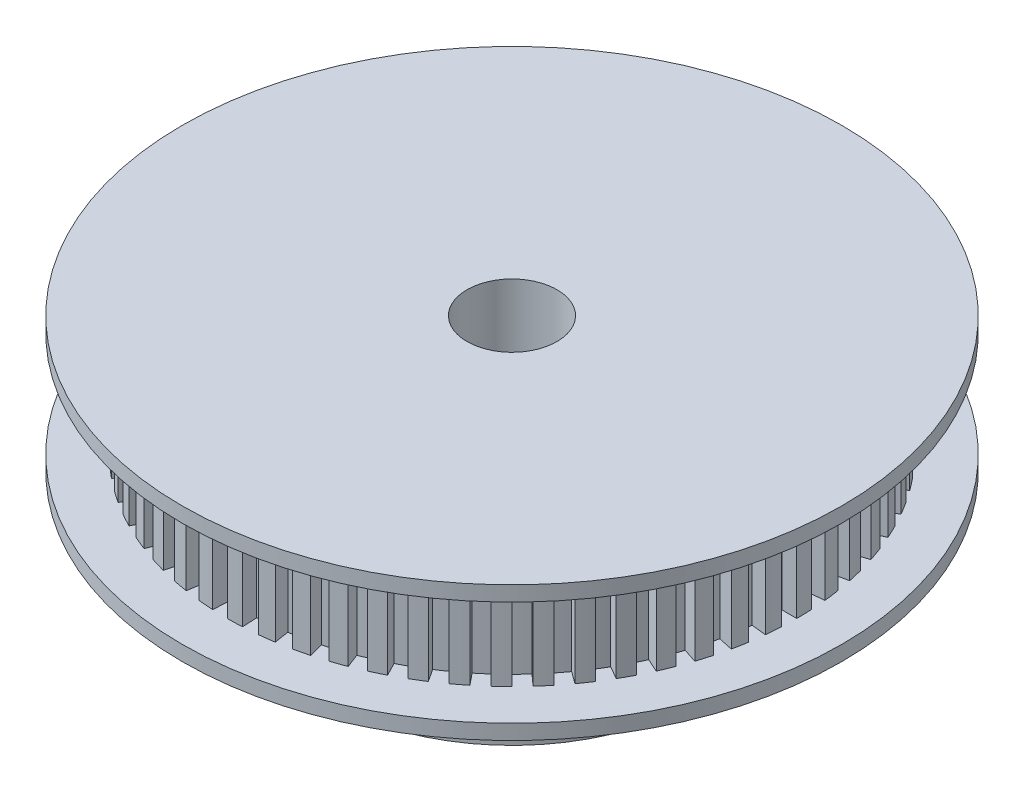
SolidWorks part; units mm, degrees
ref_plane "Front Plane" through (0, 0, 0) normal (0, 0, 1) x (1, 0, 0)
ref_plane "Top Plane" through (0, 0, 0) normal (0, 1, 0) x (1, 0, 0)
ref_plane "Right Plane" through (0, 0, 0) normal (1, 0, 0) x (0, 0, -1)
sketch "Sketch1" plane through (0, 0, 0) normal (0, 1, 0) x (1, 0, 0)
  line L1 (-12.5, -12.5) -> (12.5, -12.5)
  line L2 (-12.5, -12.5) -> (-12.5, 12.5)
  line L3 (-12.5, 12.5) -> (12.5, 12.5)
  line L4 (12.5, -12.5) -> (12.5, 12.5)
  line L5 (-12.5, -12.5) -> (12.5, 12.5) construction
  line L6 (-12.5, 12.5) -> (12.5, -12.5) construction
extrude "Boss-Extrude1" add sketch "Sketch1" along normal blind 7
sketch "Sketch2" plane through (0, 7, 0) normal (0, 1, 0) x (1, 0, 0)
  circle A0 centre (0, 0) radius 22
  dimension "D1" = 44
extrude "Boss-Extrude2" add sketch "Sketch2" along normal blind 1
sketch "Sketch4" plane through (0, 8, 0) normal (0, 1, 0) x (1, 0, 0)
  line L0 (0, 19) -> (0, 18)
  line L1 (0.9944, 18.974) -> (0.942, 17.9753)
  line L2 (1.986, 18.8959) -> (1.8815, 17.9014)
  line L3 (2.9723, 18.7661) -> (2.8158, 17.7784)
  line L4 (3.9503, 18.5848) -> (3.7424, 17.6067)
  line L5 (4.9176, 18.3526) -> (4.6587, 17.3867)
  line L6 (5.8713, 18.0701) -> (5.5623, 17.119)
  line L7 (6.809, 17.738) -> (6.4506, 16.8044)
  line L8 (7.728, 17.3574) -> (7.3213, 16.4438)
  line L9 (8.6258, 16.9291) -> (8.1718, 16.0381)
  line L10 (9.5, 16.4545) -> (9, 15.5885)
  line L11 (10.3481, 15.9347) -> (9.8035, 15.0961)
  line L12 (11.1679, 15.3713) -> (10.5801, 14.5623)
  line L13 (11.9571, 14.7658) -> (11.3278, 13.9886)
  line L14 (12.7135, 14.1198) -> (12.0444, 13.3766)
  line L15 (13.435, 13.435) -> (12.7279, 12.7279)
  line L16 (14.1198, 12.7135) -> (13.3766, 12.0444)
  line L17 (14.7658, 11.9571) -> (13.9886, 11.3278)
  line L18 (15.3713, 11.1679) -> (14.5623, 10.5801)
  line L19 (15.9347, 10.3481) -> (15.0961, 9.8035)
  line L20 (16.4545, 9.5) -> (15.5885, 9)
  line L21 (16.9291, 8.6258) -> (16.0381, 8.1718)
  line L22 (17.3574, 7.728) -> (16.4438, 7.3213)
  line L23 (17.738, 6.809) -> (16.8044, 6.4506)
  line L24 (18.0701, 5.8713) -> (17.119, 5.5623)
  line L25 (18.3526, 4.9176) -> (17.3867, 4.6587)
  line L26 (18.5848, 3.9503) -> (17.6067, 3.7424)
  line L27 (18.7661, 2.9723) -> (17.7784, 2.8158)
  line L28 (18.8959, 1.986) -> (17.9014, 1.8815)
  line L29 (18.974, 0.9944) -> (17.9753, 0.942)
  line L30 (19, 0) -> (18, 0)
  line L31 (18.974, -0.9944) -> (17.9753, -0.942)
  line L32 (18.8959, -1.986) -> (17.9014, -1.8815)
  line L33 (18.7661, -2.9723) -> (17.7784, -2.8158)
  line L34 (18.5848, -3.9503) -> (17.6067, -3.7424)
  line L35 (18.3526, -4.9176) -> (17.3867, -4.6587)
  line L36 (18.0701, -5.8713) -> (17.119, -5.5623)
  line L37 (17.738, -6.809) -> (16.8044, -6.4506)
  line L38 (17.3574, -7.728) -> (16.4438, -7.3213)
  line L39 (16.9291, -8.6258) -> (16.0381, -8.1718)
  line L40 (16.4545, -9.5) -> (15.5885, -9)
  line L41 (15.9347, -10.3481) -> (15.0961, -9.8035)
  line L42 (15.3713, -11.1679) -> (14.5623, -10.5801)
  line L43 (14.7658, -11.9571) -> (13.9886, -11.3278)
  line L44 (14.1198, -12.7135) -> (13.3766, -12.0444)
  line L45 (13.435, -13.435) -> (12.7279, -12.7279)
  line L46 (12.7135, -14.1198) -> (12.0444, -13.3766)
  line L47 (11.9571, -14.7658) -> (11.3278, -13.9886)
  line L48 (11.1679, -15.3713) -> (10.5801, -14.5623)
  line L49 (10.3481, -15.9347) -> (9.8035, -15.0961)
  line L50 (9.5, -16.4545) -> (9, -15.5885)
  line L51 (8.6258, -16.9291) -> (8.1718, -16.0381)
  line L52 (7.728, -17.3574) -> (7.3213, -16.4438)
  line L53 (6.809, -17.738) -> (6.4506, -16.8044)
  line L54 (5.8713, -18.0701) -> (5.5623, -17.119)
  line L55 (4.9176, -18.3526) -> (4.6587, -17.3867)
  line L56 (3.9503, -18.5848) -> (3.7424, -17.6067)
  line L57 (2.9723, -18.7661) -> (2.8158, -17.7784)
  line L58 (1.986, -18.8959) -> (1.8815, -17.9014)
  line L59 (0.9944, -18.974) -> (0.942, -17.9753)
  line L60 (0, -19) -> (0, -18)
  line L61 (-0.9944, -18.974) -> (-0.942, -17.9753)
  line L62 (-1.986, -18.8959) -> (-1.8815, -17.9014)
  line L63 (-2.9723, -18.7661) -> (-2.8158, -17.7784)
  line L64 (-3.9503, -18.5848) -> (-3.7424, -17.6067)
  line L65 (-4.9176, -18.3526) -> (-4.6587, -17.3867)
  line L66 (-5.8713, -18.0701) -> (-5.5623, -17.119)
  line L67 (-6.809, -17.738) -> (-6.4506, -16.8044)
  line L68 (-7.728, -17.3574) -> (-7.3213, -16.4438)
  line L69 (-8.6258, -16.9291) -> (-8.1718, -16.0381)
  line L70 (-9.5, -16.4545) -> (-9, -15.5885)
  line L71 (-10.3481, -15.9347) -> (-9.8035, -15.0961)
  line L72 (-11.1679, -15.3713) -> (-10.5801, -14.5623)
  line L73 (-11.9571, -14.7658) -> (-11.3278, -13.9886)
  line L74 (-12.7135, -14.1198) -> (-12.0444, -13.3766)
  line L75 (-13.435, -13.435) -> (-12.7279, -12.7279)
  line L76 (-14.1198, -12.7135) -> (-13.3766, -12.0444)
  line L77 (-14.7658, -11.9571) -> (-13.9886, -11.3278)
  line L78 (-15.3713, -11.1679) -> (-14.5623, -10.5801)
  line L79 (-15.9347, -10.3481) -> (-15.0961, -9.8035)
  line L80 (-16.4545, -9.5) -> (-15.5885, -9)
  line L81 (-16.9291, -8.6258) -> (-16.0381, -8.1718)
  line L82 (-17.3574, -7.728) -> (-16.4438, -7.3213)
  line L83 (-17.738, -6.809) -> (-16.8044, -6.4506)
  line L84 (-18.0701, -5.8713) -> (-17.119, -5.5623)
  line L85 (-18.3526, -4.9176) -> (-17.3867, -4.6587)
  line L86 (-18.5848, -3.9503) -> (-17.6067, -3.7424)
  line L87 (-18.7661, -2.9723) -> (-17.7784, -2.8158)
  line L88 (-18.8959, -1.986) -> (-17.9014, -1.8815)
  line L89 (-18.974, -0.9944) -> (-17.9753, -0.942)
  line L90 (-19, 0) -> (-18, 0)
  line L91 (-18.974, 0.9944) -> (-17.9753, 0.942)
  line L92 (-18.8959, 1.986) -> (-17.9014, 1.8815)
  line L93 (-18.7661, 2.9723) -> (-17.7784, 2.8158)
  line L94 (-18.5848, 3.9503) -> (-17.6067, 3.7424)
  line L95 (-18.3526, 4.9176) -> (-17.3867, 4.6587)
  line L96 (-18.0701, 5.8713) -> (-17.119, 5.5623)
  line L97 (-17.738, 6.809) -> (-16.8044, 6.4506)
  line L98 (-17.3574, 7.728) -> (-16.4438, 7.3213)
  line L99 (-16.9291, 8.6258) -> (-16.0381, 8.1718)
  line L100 (-16.4545, 9.5) -> (-15.5885, 9)
  line L101 (-15.9347, 10.3481) -> (-15.0961, 9.8035)
  line L102 (-15.3713, 11.1679) -> (-14.5623, 10.5801)
  line L103 (-14.7658, 11.9571) -> (-13.9886, 11.3278)
  line L104 (-14.1198, 12.7135) -> (-13.3766, 12.0444)
  line L105 (-13.435, 13.435) -> (-12.7279, 12.7279)
  line L106 (-12.7135, 14.1198) -> (-12.0444, 13.3766)
  line L107 (-11.9571, 14.7658) -> (-11.3278, 13.9886)
  line L108 (-11.1679, 15.3713) -> (-10.5801, 14.5623)
  line L109 (-10.3481, 15.9347) -> (-9.8035, 15.0961)
  line L110 (-9.5, 16.4545) -> (-9, 15.5885)
  line L111 (-8.6258, 16.9291) -> (-8.1718, 16.0381)
  line L112 (-7.728, 17.3574) -> (-7.3213, 16.4438)
  line L113 (-6.809, 17.738) -> (-6.4506, 16.8044)
  line L114 (-5.8713, 18.0701) -> (-5.5623, 17.119)
  line L115 (-4.9176, 18.3526) -> (-4.6587, 17.3867)
  line L116 (-3.9503, 18.5848) -> (-3.7424, 17.6067)
  line L117 (-2.9723, 18.7661) -> (-2.8158, 17.7784)
  line L118 (-1.986, 18.8959) -> (-1.8815, 17.9014)
  line L119 (-0.9944, 18.974) -> (-0.942, 17.9753)
  arc A2 (0.9944, 18.974) -> (1.986, 18.8959) centre (0, 0) cw
  arc A3 (1.8815, 17.9014) -> (2.8158, 17.7784) centre (0, 0) cw
  arc A4 (3.7424, 17.6067) -> (4.6587, 17.3867) centre (0, 0) cw
  arc A5 (2.9723, 18.7661) -> (3.9503, 18.5848) centre (0, 0) cw
  arc A6 (5.5623, 17.119) -> (6.4506, 16.8044) centre (0, 0) cw
  arc A7 (4.9176, 18.3526) -> (5.8713, 18.0701) centre (0, 0) cw
  arc A8 (7.3213, 16.4438) -> (8.1718, 16.0381) centre (0, 0) cw
  arc A9 (6.809, 17.738) -> (7.728, 17.3574) centre (0, 0) cw
  arc A10 (9, 15.5885) -> (9.8035, 15.0961) centre (0, 0) cw
  arc A11 (8.6258, 16.9291) -> (9.5, 16.4545) centre (0, 0) cw
  arc A12 (10.5801, 14.5623) -> (11.3278, 13.9886) centre (0, 0) cw
  arc A13 (10.3481, 15.9347) -> (11.1679, 15.3713) centre (0, 0) cw
  arc A14 (12.0444, 13.3766) -> (12.7279, 12.7279) centre (0, 0) cw
  arc A15 (11.9571, 14.7658) -> (12.7135, 14.1198) centre (0, 0) cw
  arc A16 (13.3766, 12.0444) -> (13.9886, 11.3278) centre (0, 0) cw
  arc A17 (13.435, 13.435) -> (14.1198, 12.7135) centre (0, 0) cw
  arc A18 (14.5623, 10.5801) -> (15.0961, 9.8035) centre (0, 0) cw
  arc A19 (14.7658, 11.9571) -> (15.3713, 11.1679) centre (0, 0) cw
  arc A20 (15.5885, 9) -> (16.0381, 8.1718) centre (0, 0) cw
  arc A21 (15.9347, 10.3481) -> (16.4545, 9.5) centre (0, 0) cw
  arc A22 (16.4438, 7.3213) -> (16.8044, 6.4506) centre (0, 0) cw
  arc A23 (16.9291, 8.6258) -> (17.3574, 7.728) centre (0, 0) cw
  arc A24 (17.119, 5.5623) -> (17.3867, 4.6587) centre (0, 0) cw
  arc A25 (17.738, 6.809) -> (18.0701, 5.8713) centre (0, 0) cw
  arc A26 (17.6067, 3.7424) -> (17.7784, 2.8158) centre (0, 0) cw
  arc A27 (18.3526, 4.9176) -> (18.5848, 3.9503) centre (0, 0) cw
  arc A28 (17.9014, 1.8815) -> (17.9753, 0.942) centre (0, 0) cw
  arc A29 (18.7661, 2.9723) -> (18.8959, 1.986) centre (0, 0) cw
  arc A30 (18, 0) -> (17.9753, -0.942) centre (0, 0) cw
  arc A31 (18.974, 0.9944) -> (19, 0) centre (0, 0) cw
  arc A32 (17.9014, -1.8815) -> (17.7784, -2.8158) centre (0, 0) cw
  arc A33 (18.974, -0.9944) -> (18.8959, -1.986) centre (0, 0) cw
  arc A34 (17.6067, -3.7424) -> (17.3867, -4.6587) centre (0, 0) cw
  arc A35 (18.7661, -2.9723) -> (18.5848, -3.9503) centre (0, 0) cw
  arc A36 (17.119, -5.5623) -> (16.8044, -6.4506) centre (0, 0) cw
  arc A37 (18.3526, -4.9176) -> (18.0701, -5.8713) centre (0, 0) cw
  arc A38 (16.4438, -7.3213) -> (16.0381, -8.1718) centre (0, 0) cw
  arc A39 (17.738, -6.809) -> (17.3574, -7.728) centre (0, 0) cw
  arc A40 (15.5885, -9) -> (15.0961, -9.8035) centre (0, 0) cw
  arc A41 (16.9291, -8.6258) -> (16.4545, -9.5) centre (0, 0) cw
  arc A42 (14.5623, -10.5801) -> (13.9886, -11.3278) centre (0, 0) cw
  arc A43 (15.9347, -10.3481) -> (15.3713, -11.1679) centre (0, 0) cw
  arc A44 (13.3766, -12.0444) -> (12.7279, -12.7279) centre (0, 0) cw
  arc A45 (14.7658, -11.9571) -> (14.1198, -12.7135) centre (0, 0) cw
  arc A46 (12.0444, -13.3766) -> (11.3278, -13.9886) centre (0, 0) cw
  arc A47 (13.435, -13.435) -> (12.7135, -14.1198) centre (0, 0) cw
  arc A48 (10.5801, -14.5623) -> (9.8035, -15.0961) centre (0, 0) cw
  arc A49 (11.9571, -14.7658) -> (11.1679, -15.3713) centre (0, 0) cw
  arc A50 (9, -15.5885) -> (8.1718, -16.0381) centre (0, 0) cw
  arc A51 (10.3481, -15.9347) -> (9.5, -16.4545) centre (0, 0) cw
  arc A52 (7.3213, -16.4438) -> (6.4506, -16.8044) centre (0, 0) cw
  arc A53 (8.6258, -16.9291) -> (7.728, -17.3574) centre (0, 0) cw
  arc A54 (5.5623, -17.119) -> (4.6587, -17.3867) centre (0, 0) cw
  arc A55 (6.809, -17.738) -> (5.8713, -18.0701) centre (0, 0) cw
  arc A56 (3.7424, -17.6067) -> (2.8158, -17.7784) centre (0, 0) cw
  arc A57 (4.9176, -18.3526) -> (3.9503, -18.5848) centre (0, 0) cw
  arc A58 (1.8815, -17.9014) -> (0.942, -17.9753) centre (0, 0) cw
  arc A59 (2.9723, -18.7661) -> (1.986, -18.8959) centre (0, 0) cw
  arc A60 (0, -18) -> (-0.942, -17.9753) centre (0, 0) cw
  arc A61 (0.9944, -18.974) -> (0, -19) centre (0, 0) cw
  arc A62 (-1.8815, -17.9014) -> (-2.8158, -17.7784) centre (0, 0) cw
  arc A63 (-0.9944, -18.974) -> (-1.986, -18.8959) centre (0, 0) cw
  arc A64 (-3.7424, -17.6067) -> (-4.6587, -17.3867) centre (0, 0) cw
  arc A65 (-2.9723, -18.7661) -> (-3.9503, -18.5848) centre (0, 0) cw
  arc A66 (-5.5623, -17.119) -> (-6.4506, -16.8044) centre (0, 0) cw
  arc A67 (-4.9176, -18.3526) -> (-5.8713, -18.0701) centre (0, 0) cw
  arc A68 (-7.3213, -16.4438) -> (-8.1718, -16.0381) centre (0, 0) cw
  arc A69 (-6.809, -17.738) -> (-7.728, -17.3574) centre (0, 0) cw
  arc A70 (-9, -15.5885) -> (-9.8035, -15.0961) centre (0, 0) cw
  arc A71 (-8.6258, -16.9291) -> (-9.5, -16.4545) centre (0, 0) cw
  arc A72 (-10.5801, -14.5623) -> (-11.3278, -13.9886) centre (0, 0) cw
  arc A73 (-10.3481, -15.9347) -> (-11.1679, -15.3713) centre (0, 0) cw
  arc A74 (-12.0444, -13.3766) -> (-12.7279, -12.7279) centre (0, 0) cw
  arc A75 (-11.9571, -14.7658) -> (-12.7135, -14.1198) centre (0, 0) cw
  arc A76 (-13.3766, -12.0444) -> (-13.9886, -11.3278) centre (0, 0) cw
  arc A77 (-13.435, -13.435) -> (-14.1198, -12.7135) centre (0, 0) cw
  arc A78 (-14.5623, -10.5801) -> (-15.0961, -9.8035) centre (0, 0) cw
  arc A79 (-14.7658, -11.9571) -> (-15.3713, -11.1679) centre (0, 0) cw
  arc A80 (-15.5885, -9) -> (-16.0381, -8.1718) centre (0, 0) cw
  arc A81 (-15.9347, -10.3481) -> (-16.4545, -9.5) centre (0, 0) cw
  arc A82 (-16.4438, -7.3213) -> (-16.8044, -6.4506) centre (0, 0) cw
  arc A83 (-16.9291, -8.6258) -> (-17.3574, -7.728) centre (0, 0) cw
  arc A84 (-17.119, -5.5623) -> (-17.3867, -4.6587) centre (0, 0) cw
  arc A85 (-17.738, -6.809) -> (-18.0701, -5.8713) centre (0, 0) cw
  arc A86 (-17.6067, -3.7424) -> (-17.7784, -2.8158) centre (0, 0) cw
  arc A87 (-18.3526, -4.9176) -> (-18.5848, -3.9503) centre (0, 0) cw
  arc A88 (-17.9014, -1.8815) -> (-17.9753, -0.942) centre (0, 0) cw
  arc A89 (-18.7661, -2.9723) -> (-18.8959, -1.986) centre (0, 0) cw
  arc A90 (-18, 0) -> (-17.9753, 0.942) centre (0, 0) cw
  arc A91 (-18.974, -0.9944) -> (-19, 0) centre (0, 0) cw
  arc A92 (-17.9014, 1.8815) -> (-17.7784, 2.8158) centre (0, 0) cw
  arc A93 (-18.974, 0.9944) -> (-18.8959, 1.986) centre (0, 0) cw
  arc A94 (-17.6067, 3.7424) -> (-17.3867, 4.6587) centre (0, 0) cw
  arc A95 (-18.7661, 2.9723) -> (-18.5848, 3.9503) centre (0, 0) cw
  arc A96 (-17.119, 5.5623) -> (-16.8044, 6.4506) centre (0, 0) cw
  arc A97 (-18.3526, 4.9176) -> (-18.0701, 5.8713) centre (0, 0) cw
  arc A98 (-16.4438, 7.3213) -> (-16.0381, 8.1718) centre (0, 0) cw
  arc A99 (-17.738, 6.809) -> (-17.3574, 7.728) centre (0, 0) cw
  arc A100 (-15.5885, 9) -> (-15.0961, 9.8035) centre (0, 0) cw
  arc A101 (-16.9291, 8.6258) -> (-16.4545, 9.5) centre (0, 0) cw
  arc A102 (-14.5623, 10.5801) -> (-13.9886, 11.3278) centre (0, 0) cw
  arc A103 (-15.9347, 10.3481) -> (-15.3713, 11.1679) centre (0, 0) cw
  arc A104 (-13.3766, 12.0444) -> (-12.7279, 12.7279) centre (0, 0) cw
  arc A105 (-14.7658, 11.9571) -> (-14.1198, 12.7135) centre (0, 0) cw
  arc A106 (-12.0444, 13.3766) -> (-11.3278, 13.9886) centre (0, 0) cw
  arc A107 (-13.435, 13.435) -> (-12.7135, 14.1198) centre (0, 0) cw
  arc A108 (-10.5801, 14.5623) -> (-9.8035, 15.0961) centre (0, 0) cw
  arc A109 (-11.9571, 14.7658) -> (-11.1679, 15.3713) centre (0, 0) cw
  arc A110 (-9, 15.5885) -> (-8.1718, 16.0381) centre (0, 0) cw
  arc A111 (-10.3481, 15.9347) -> (-9.5, 16.4545) centre (0, 0) cw
  arc A112 (-7.3213, 16.4438) -> (-6.4506, 16.8044) centre (0, 0) cw
  arc A113 (-8.6258, 16.9291) -> (-7.728, 17.3574) centre (0, 0) cw
  arc A114 (-5.5623, 17.119) -> (-4.6587, 17.3867) centre (0, 0) cw
  arc A115 (-6.809, 17.738) -> (-5.8713, 18.0701) centre (0, 0) cw
  arc A116 (-3.7424, 17.6067) -> (-2.8158, 17.7784) centre (0, 0) cw
  arc A117 (-4.9176, 18.3526) -> (-3.9503, 18.5848) centre (0, 0) cw
  arc A118 (-1.8815, 17.9014) -> (-0.942, 17.9753) centre (0, 0) cw
  arc A119 (-2.9723, 18.7661) -> (-1.986, 18.8959) centre (0, 0) cw
  arc A120 (0, 18) -> (0.942, 17.9753) centre (0, 0) cw
  arc A121 (-0.9944, 18.974) -> (0, 19) centre (0, 0) cw
  point P247 (0, 0)
  point P485 (0, 0)
  dimension "D1" = 60
  dimension "D3" = 1
extrude "Boss-Extrude3" add sketch "Sketch4" along normal blind 7
sketch "Sketch5" plane through (0, 15, 0) normal (0, 1, 0) x (1, 0, 0)
  circle A0 centre (0, 0) radius 22
  dimension "D1" = 44
extrude "Boss-Extrude4" add sketch "Sketch5" along normal blind 1
sketch "Sketch6" plane through (12.5, 0, 0) normal (1, 0, 0) x (0, 0, -1)
  circle A0 centre (0, 4) radius 2
  point P2 (0, 0)
  dimension "D1" = 4
  dimension "D2" = 4
sketch "Sketch8" plane through (0, 0, -12.5) normal (0, 0, -1) x (-1, 0, 0)
  line L0 (-12.5, 0) -> (12.5, 0) construction
  circle A0 centre (0, 4.0024) radius 2
  point P2 (0.1019, 0.0024)
  point P3 (0, 0)
  dimension "D1" = 4
  dimension "D2" = 4.0024
extrude "Cut-Extrude1" cut sketch "Sketch6" against normal blind 5 contours A0
extrude "Cut-Extrude2" cut sketch "Sketch8" against normal blind 5 contours A0
thread "Thread1" pitch 0.7 method extrude profile "Thread Profile1" start angle 0, offset 0, length 5, pitch 0.7, diameter 4
ref_plane "Plane1" through (12.5, 4, 2) normal (0, -1, 0) x (0, 0, 1)
sketch "Thread Profile1" plane through (12.5, 4, 2) normal (0, -1, 0) x (0, 0, 1)
  line L0 (0, 0) -> (0, 0.7) construction
  line L11 (0, 0) -> (0, 0.6125)
  line L12 (0, 0.6125) -> (-0.3789, 0.3937)
  line L13 (-0.3789, 0.3937) -> (-0.3789, 0.2187)
  line L15 (-0.3789, 0.2187) -> (0, 0)
  line L17 (-0.3789, 0.3062) -> (0, 0.3062) construction
  point P2 (0, 0)
  dimension "Pitch" = 0.7
  dimension "Profile_Angle" = 60
  dimension "Profile_Land" = 0.175
  dimension "Profile_Height" = 0.3789
thread "Thread2" pitch 0.7 method extrude profile "Thread Profile2" start angle 0, offset 0, length 5, pitch 0.7, diameter 4
ref_plane "Plane2" through (2, 4.0024, -12.5) normal (0, -1, 0) x (1, 0, 0)
sketch "Thread Profile2" plane through (2, 4.0024, -12.5) normal (0, -1, 0) x (1, 0, 0)
  line L0 (0, 0) -> (0, 0.7) construction
  line L11 (0, 0) -> (0, 0.6125)
  line L12 (0, 0.6125) -> (-0.3789, 0.3937)
  line L13 (-0.3789, 0.3937) -> (-0.3789, 0.2187)
  line L15 (-0.3789, 0.2187) -> (0, 0)
  line L17 (-0.3789, 0.3062) -> (0, 0.3062) construction
  point P2 (0, 0)
  dimension "Pitch" = 0.7
  dimension "Profile_Angle" = 60
  dimension "Profile_Land" = 0.175
  dimension "Profile_Height" = 0.3789
sketch "Sketch13" plane through (0, 0, 0) normal (0, -1, 0) x (1, 0, 0)
  line L1 (-12.5, -12.5) -> (12.5, -12.5)
  line L2 (-12.5, -12.5) -> (-12.5, 12.5)
  line L3 (-12.5, 12.5) -> (12.5, 12.5)
  line L4 (12.5, -12.5) -> (12.5, 12.5)
  line L5 (-12.5, -12.5) -> (12.5, 12.5) construction
  line L6 (-12.5, 12.5) -> (12.5, -12.5) construction
  circle A0 centre (0, 0) radius 3
  circle A1 centre (0, 0) radius 12.5
  line M1 (12.5, -12.5) -> (12.5, 12.5)
  line M2 (12.5, 12.5) -> (-12.5, 12.5)
  line M3 (-12.5, 12.5) -> (-12.5, -12.5)
  line M4 (-12.5, -12.5) -> (12.5, -12.5)
  dimension "D1" = 6
  dimension "D2" = 25
extrude "Cut-Extrude3" cut sketch "Sketch13" against normal up to next and the other way blind 10 contours A0 region at (0, 0, 0)
extrude "Cut-Extrude4" cut sketch "Sketch13<3>" against normal up to surface (7 mm away) contours A1 L4 M2 | A1 L3 M3 | A1 L2 M4 | A1 L1 M1 region at (-9.7079, 0, -9.7079) region at (9.7079, 0, -9.7079) region at (-9.7079, 0, 9.7079) region at (9.7079, 0, 9.7079) body kept at (22, 15, 0) up to face at (0, 7, 22)
sketch "Sketch13<3>" plane through (0, 0, 0) normal (0, -1, 0) x (1, 0, 0) same geometry as "Sketch13"
